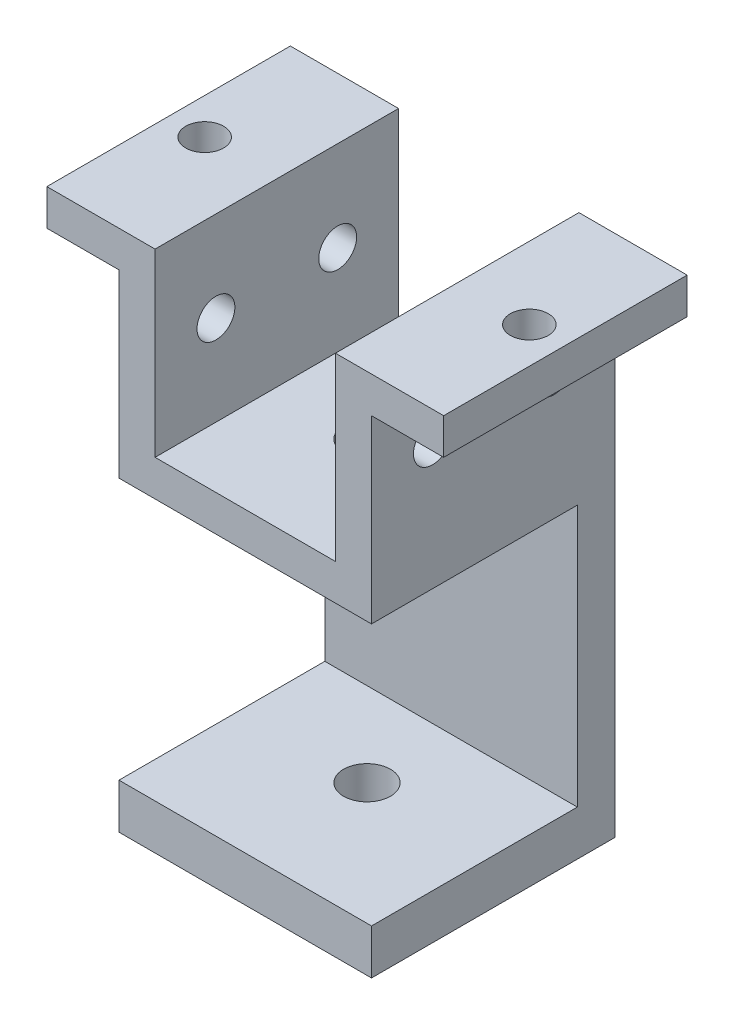
SolidWorks part; units mm, degrees
material "PET"
ref_plane "Front Plane" through (0, 0, 0) normal (0, 0, 1) x (1, 0, 0)
ref_plane "Top Plane" through (0, 0, 0) normal (0, 1, 0) x (1, 0, 0)
ref_plane "Right Plane" through (0, 0, 0) normal (1, 0, 0) x (0, 0, -1)
sketch "Sketch1" plane through (0, 0, 0) normal (0, 0, 1) x (1, 0, 0)
  line L0 (-14, 0) -> (14, 0)
  line L1 (14, 0) -> (14, 20)
  line L2 (14, 20) -> (22, 20)
  line L3 (22, 20) -> (22, 24)
  line L4 (22, 24) -> (10, 24)
  line L5 (10, 24) -> (10, 4)
  line L6 (10, 4) -> (-10, 4)
  line L7 (-10, 4) -> (-10, 24)
  line L8 (-10, 24) -> (-22, 24)
  line L9 (-22, 24) -> (-22, 20)
  line L10 (-22, 20) -> (-14, 20)
  line L11 (-14, 20) -> (-14, 0)
  dimension "D1" = 28
  dimension "D2" = 20
  dimension "D3" = 4
  dimension "D4" = 4
  dimension "D5" = 4
  dimension "D6" = 44
  dimension "D7" = 8
  dimension "D8" = 20
extrude "Boss-Extrude1" add sketch "Sketch1" along normal blind 27
sketch "Sketch2" plane through (-14, 0, 0) normal (-1, 0, 0) x (0, 0, 1)
  line L0 (13.5, 24) -> (13.5, 0) construction
  line L2 (13.5, 24) -> (0, 4) construction
  line L3 (27, 24) -> (0, 24) construction
  line L4 (27, 0) -> (0, 0) construction
  line L5 (13.5, 24) -> (27, 4) construction
  line L6 (27, 0) -> (27, 20) construction
  circle A0 centre (6.75, 14) radius 2.1
  circle A1 centre (20.25, 14) radius 2.1
  dimension "D2" = 4.2
  dimension "D3" = 4.2
  dimension "D1" = 4
extrude "Cut-Extrude1" cut sketch "Sketch2" against normal through all
sketch "Sketch3" plane through (0, 20, 0) normal (0, -1, 0) x (1, 0, 0)
  line L0 (-22, 13.5) -> (22, 13.5) construction
  line L1 (-22, 27) -> (-22, 0) construction
  line L2 (22, 27) -> (22, 0) construction
  circle A0 centre (-18, 13.5) radius 2.1
  circle A1 centre (18, 13.5) radius 2.1
  dimension "D1" = 4.2
  dimension "D2" = 4.2
  dimension "D3" = 36
  dimension "D4" = 4
extrude "Cut-Extrude2" cut sketch "Sketch3" against normal through all
sketch "Sketch5" plane through (0, 0, 0) normal (0, -1, 0) x (1, 0, 0)
  line L0 (14, 27) -> (14, 0) construction
  line L1 (-14, 0) -> (14, 0)
  line L2 (-14, 0) -> (-14, 4.1767)
  line L3 (-14, 4.1767) -> (14, 4.1767)
  line L4 (14, 0) -> (14, 4.1767)
extrude "Boss-Extrude2" add sketch "Sketch5" along normal blind 34
sketch "Sketch6" plane through (0, 0, 4.1767) normal (0, 0, 1) x (1, 0, 0)
  line L0 (14, -34) -> (14, 0) construction
  line L1 (-14, -34) -> (14, -34)
  line L2 (-14, -34) -> (-14, -29)
  line L3 (-14, -29) -> (14, -29)
  line L4 (14, -34) -> (14, -29)
  dimension "D1" = 5
extrude "Boss-Extrude3" add sketch "Sketch6" along normal up to surface (22.8233 mm away) up to face at (0, 15.3333, 27)
sketch "Sketch7" plane through (0, -34, 0) normal (0, -1, 0) x (1, 0, 0)
  line L0 (0, 0) -> (0, 27) construction
  line L1 (-14, 27) -> (14, 27) construction
  circle A0 centre (0, 13.5) radius 2.6
  dimension "D1" = 5.2
extrude "Cut-Extrude3" cut sketch "Sketch7" against normal through all
ref_axis "Axis1" through (0, -29, 13.5) along (0, -1, 0)
ref_plane "Plane1" through (0, 0, 13.5) normal (0, 0, 1) x (1, 0, 0)
